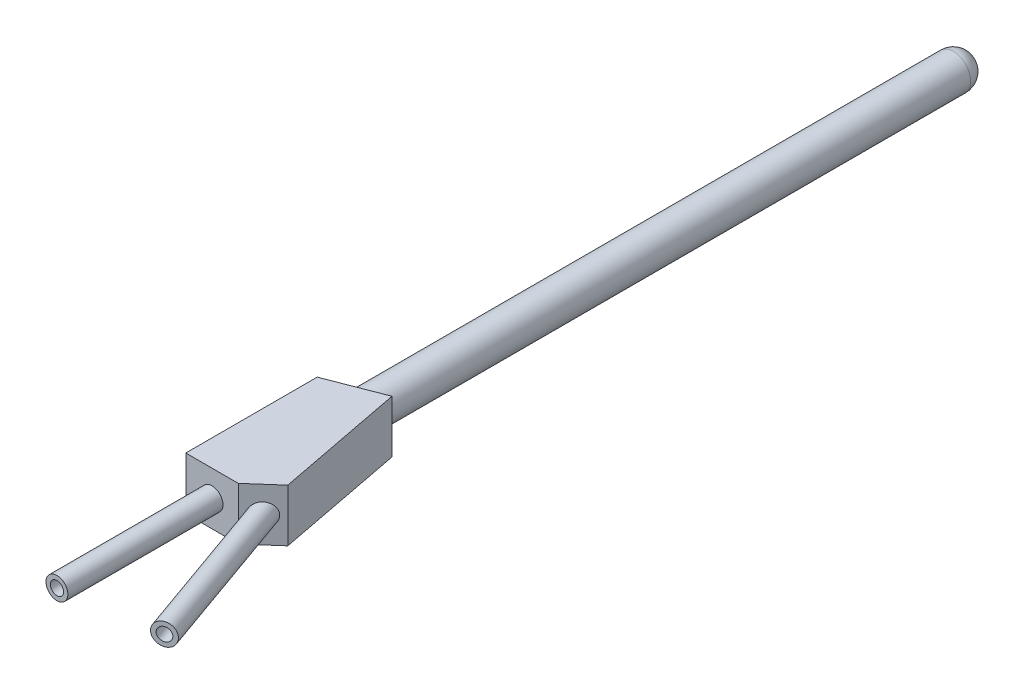
SolidWorks part; units mm, degrees
ref_plane "Front Plane" through (0, 0, 0) normal (0, 0, 1) x (1, 0, 0)
ref_plane "Top Plane" through (0, 0, 0) normal (0, 1, 0) x (1, 0, 0)
ref_plane "Right Plane" through (0, 0, 0) normal (1, 0, 0) x (0, 0, -1)
sketch "Sketch1" plane through (0, 0, 0) normal (0, 1, 0) x (1, 0, 0)
  line L0 (0, 0) -> (6.1582, 2.3741)
  line L1 (6.1582, 2.3741) -> (9, -12.3542)
  line L2 (9, -12.3542) -> (6, -15)
  line L3 (6, -15) -> (0, -15)
  line L4 (0, -15) -> (0, 0)
  dimension "D1" = 15
  dimension "D2" = 6.6
  dimension "D3" = 15
  dimension "D4" = 6
  dimension "D5" = 9
  dimension "D6" = 4
extrude "Boss-Extrude1" add sketch "Sketch1" along normal blind 6
sketch "Sketch4" plane through (0, 0, 0) normal (0, 0, 1) x (1, 0, 0)
  line L0 (0, 0) -> (6.1582, 6) construction
  line L1 (0, 6) -> (6.1582, 0) construction
  circle A0 centre (3.0791, 3) radius 2
  point P10 (3.0791, 3)
  dimension "D1" = 4
extrude "Boss-Extrude2" add sketch "Sketch4" against normal blind 71.5
fillet "Fillet1" radius 2 1 edges at (5.0791, 3, -71.5)
sketch "Sketch5" plane through (0, 0, 15) normal (0, 0, 1) x (1, 0, 0)
  line L0 (0, 0) -> (6, 0) construction
  line L1 (0, 6) -> (0, 0) construction
  circle A0 centre (3, 3) radius 1.25
  dimension "D1" = 2.5
  dimension "D2" = 3
  dimension "D3" = 3
extrude "Boss-Extrude3" add sketch "Sketch5" along normal blind 17.7
sketch "Sketch6" plane through (0, 6, 0) normal (0, 1, 0) x (1, 0, 0)
  line L0 (2.3298, 0.8982) -> (7.5, -13.6771) construction
  line L1 (6, -15) -> (9, -12.3542) construction
  line L2 (6.1582, 2.3741) -> (0, 0) construction
ref_plane "Plane1" through (7.5, 6, 13.6771) normal (0.3343, 0, 0.9425) x (0.9425, 0, -0.3343)
sketch "Sketch7" plane through (7.5, 6, 13.6771) normal (0.3343, 0, 0.9425) x (0.9425, 0, -0.3343)
  line L0 (1.8559, 0) -> (1.8559, -6) construction
  line L2 (-1.8559, -6) -> (1.8559, -6) construction
  circle A0 centre (0.0009, -3) radius 1.25
  dimension "D1" = 2.5
  dimension "D2" = 1.855
  dimension "D3" = 3
extrude "Boss-Extrude4" add sketch "Sketch7" along normal blind 18.5
extrude "Boss-Extrude5" add sketch "Sketch7<2>" against normal blind 5
sketch "Sketch7<2>" plane through (7.5, 6, 13.6771) normal (0.3343, 0, 0.9425) x (0.9425, 0, -0.3343) same geometry as "Sketch7"
shell "Shell1" thickness 0.5 removed face at (4.25, 3, 32.7) removed face at (14.8638, 3, 30.6945)
